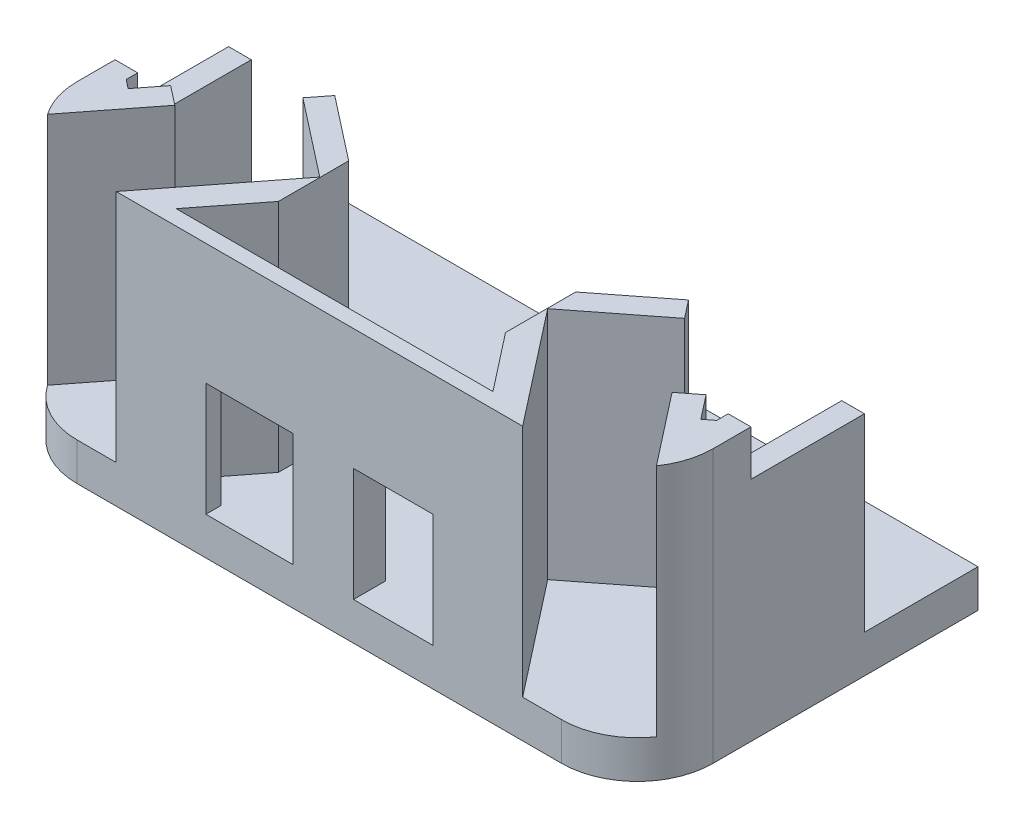
SolidWorks part; units mm, degrees
ref_plane "前视基准面" through (0, 0, 0) normal (0, 0, 1) x (1, 0, 0)
ref_plane "上视基准面" through (0, 0, 0) normal (0, 1, 0) x (1, 0, 0)
ref_plane "右视基准面" through (0, 0, 0) normal (1, 0, 0) x (0, 0, -1)
sketch "草图1" plane through (0, 0, 0) normal (0, 1, 0) x (1, 0, 0)
  line L1 (-42, 15) -> (42, 15)
  line L2 (-42, 15) -> (-42, -15)
  line L3 (-42, -15) -> (42, -15)
  line L4 (42, 15) -> (42, -15)
  line L5 (-42, 15) -> (42, -15) construction
  line L6 (-42, -15) -> (42, 15) construction
  point P0 (0, 0)
  dimension "D1" = 84
  dimension "D2" = 30
extrude "凸台-拉伸1" add sketch "草图1" along normal blind 34
sketch "草图2" plane through (0, 34, 0) normal (0, 1, 0) x (1, 0, 0)
  line L0 (-39, 15) -> (-3.1616, -13)
  line L1 (42, 15) -> (-42, 15) construction
  line L2 (-3.1616, -13) -> (3.1616, -13)
  line L3 (3.1616, -13) -> (39, 15)
  line L4 (-39, 15) -> (39, 15)
  line L5 (-42, 15) -> (-42, -15) construction
  line L6 (-42, -15) -> (42, -15) construction
  dimension "D1" = 38
  dimension "D2" = 3
  dimension "D3" = 3
  dimension "D4" = 2
  dimension "D5" = 38
extrude "切除-拉伸1" cut sketch "草图2" against normal blind 30
sketch "草图3" plane through (0, 34, 0) normal (0, 1, 0) x (1, 0, 0)
  line L0 (-26.357, 5.1222) -> (-42, -14.9)
  line L1 (42, -14.9) -> (26.357, 5.1222)
  line L2 (-39, 15) -> (-3.1616, -13) construction
  line L3 (42, -15) -> (42, 15) construction
  line L4 (-42, 15) -> (-42, -15) construction
  line L5 (-42, -14.9) -> (-42, -15)
  line L6 (0, 15) -> (0, -15) construction
  line L7 (3.1616, -13) -> (39, 15) construction
  line L8 (-42, -15) -> (-26.8499, -15)
  line L9 (-42, -15) -> (42, -15) construction
  line L10 (-26.8499, -15) -> (-16.9008, -2.2658)
  line L11 (-16.9008, -2.2658) -> (-26.357, 5.1222)
  line L12 (26.357, 5.1222) -> (16.9008, -2.2658)
  line L13 (16.9008, -2.2658) -> (26.8499, -15)
  line L14 (26.8499, -15) -> (42, -15)
  line L15 (42, -15) -> (42, -14.9)
  dimension "D1" = 12
  dimension "D2" = 0.1
  dimension "D3" = 12
  dimension "D4" = 0.1
sketch "草图4" plane through (0, 0, 15) normal (0, 0, 1) x (1, 0, 0)
  line L0 (0, 34) -> (0, 0) construction
  line L1 (-42, 34) -> (42, 34) construction
  line L2 (-15, 34) -> (-15, 16)
  line L3 (-15, 34) -> (15, 34)
  line L4 (0, 34) -> (0, 16)
  line L5 (-15, 16) -> (15, 16)
  line L6 (15, 34) -> (15, 16)
  line M3 (42, 34) -> (-42, 34)
  dimension "D1" = 18
  dimension "D2" = 15
extrude "切除-拉伸4" cut sketch "草图4" against normal blind 30 contours L2 L5 L4 L3 | L6 L4 L5 M3 region at (-7.5, 25, 15) region at (7.5, 25, 15)
extrude "切除-拉伸6" cut sketch "草图3" against normal blind 30
sketch "草图6" plane through (0, 4, 0) normal (0, 1, 0) x (1, 0, 0)
  line L0 (-24.51, 7.4862) -> (-15.0538, 0.0983)
  line L1 (-26.357, 5.1222) -> (-42, -14.9) construction
  line L2 (-26.8499, -15) -> (-16.9008, -2.2658) construction
  line L3 (-15.0538, 0.0983) -> (-13.2069, 2.4623)
  line L4 (-13.2069, 2.4623) -> (-22.663, 9.8502)
  line L5 (-22.663, 9.8502) -> (-24.51, 7.4862)
  line L6 (13.2069, 2.4623) -> (22.663, 9.8502)
  line L7 (16.9008, -2.2658) -> (26.8499, -15) construction
  line L8 (42, -14.9) -> (26.357, 5.1222) construction
  line L9 (22.663, 9.8502) -> (24.51, 7.4862)
  line L10 (42, -14.9) -> (26.357, 5.1222) construction
  line L11 (24.51, 7.4862) -> (15.0538, 0.0983)
  line L12 (16.9008, -2.2658) -> (26.8499, -15) construction
  line L13 (15.0538, 0.0983) -> (13.2069, 2.4623)
  line L17 (-39, 15) -> (-26.357, 5.1222) construction
  line L18 (26.357, 5.1222) -> (39, 15) construction
  dimension "D1" = 3
  dimension "D2" = 3
  dimension "D3" = 3
  dimension "D4" = 3
sketch "草图8" plane through (0, 34, 0) normal (0, 1, 0) x (1, 0, 0)
  line L0 (42, -14.9) -> (42, 15) construction
  line L1 (-39, 15) -> (39, 15)
  line L2 (-39, 15) -> (-39, -13)
  line L3 (-39, -13) -> (39, -13)
  line L4 (39, 15) -> (39, -13)
  line L5 (26.8499, -15) -> (42, -15) construction
  dimension "D1" = 3
  dimension "D2" = 2
extrude "切除-拉伸7" cut sketch "草图8" against normal blind 30
extrude "凸台-拉伸4" add sketch "草图6" along normal blind 30
sketch "草图9" plane through (0, 4, 0) normal (0, 1, 0) x (1, 0, 0)
  line L0 (-25.2873, -13) -> (-13.2069, 2.4623)
  line L1 (-13.2069, 2.4623) -> (-13.2069, -13)
  line L2 (-25.2873, -13) -> (25.2873, -13) construction
  line L3 (-13.2069, -13) -> (-24.5296, -13)
  line L4 (0, -13) -> (0, 15) construction
  line L5 (-15, -13) -> (15, -13) construction
  line L6 (39, 15) -> (-39, 15) construction
  line L7 (13.2069, -13) -> (24.5296, -13)
  line L8 (13.2069, 2.4623) -> (13.2069, -13)
  line L9 (25.2873, -13) -> (13.2069, 2.4623)
  line M4 (-13.2069, 2.4623) -> (-15.0538, 0.0983)
  line M14 (-25.2873, -13) -> (25.2873, -13)
  line M17 (15.0538, 0.0983) -> (13.2069, 2.4623)
extrude "凸台-拉伸5" add sketch "草图9" along normal blind 30 contours L9 L8 M14 M17 | L1 L0 M4 M14 region at (17.2337, 4, 7.8459) region at (-17.2337, 4, 7.8459)
sketch "草图11" plane through (0, 0, 13) normal (0, 0, 1) x (1, 0, 0)
  line L1 (-15, 34) -> (15, 34)
  line L2 (-15, 34) -> (-15, 16)
  line L3 (-15, 16) -> (15, 16)
  line L4 (15, 34) -> (15, 16)
extrude "切除-拉伸9" cut sketch "草图11" against normal through all
sketch "草图14" plane through (0, 34, 0) normal (0, 1, 0) x (1, 0, 0)
  line L0 (-20.9247, -13) -> (-15, -5.4167)
  line L1 (-15, 3.8633) -> (-15, -15) construction
  line L2 (-15, -5.4167) -> (-15, -13)
  line L3 (-15, -13) -> (-20.9247, -13)
  line L4 (-26.8499, -15) -> (-15, -15) construction
  line L5 (-26.8499, -15) -> (-15.0538, 0.0983) construction
  line L6 (-15, -5.4167) -> (-15, -13)
  line L7 (0, 15) -> (0, -15) construction
  line L8 (39, 15) -> (-39, 15) construction
  line L9 (-15, -15) -> (15, -15) construction
  line L10 (15, -5.4167) -> (15, -13)
  line L11 (15, -13) -> (20.9247, -13)
  line L12 (15, -5.4167) -> (15, -13)
  line L13 (20.9247, -13) -> (15, -5.4167)
  line M1 (-15, -15) -> (-15, 3.8633)
  dimension "D1" = 2
  dimension "D2" = 0
extrude "切除-拉伸12" cut sketch "草图14" against normal blind 30 contours L3 L0 M1 | L11 L13 L10 region at (-16.9749, 34, 10.4722) region at (16.9749, 34, 10.4722)
sketch "草图17" plane through (0, 4, 0) normal (0, 1, 0) x (1, 0, 0)
  line L0 (-22.663, 9.8502) -> (-23.3928, 10.4204)
  line L1 (-23.3928, 10.4204) -> (-25.2397, 8.0564)
  line L2 (-25.2397, 8.0564) -> (-24.51, 7.4862)
  line L3 (-24.51, 7.4862) -> (-22.663, 9.8502)
  line L4 (22.663, 9.8502) -> (23.3597, 10.3946)
  line L5 (23.3597, 10.3946) -> (25.2067, 8.0305)
  line L6 (25.2067, 8.0305) -> (24.51, 7.4862)
  line L7 (24.51, 7.4862) -> (22.663, 9.8502)
extrude "凸台-拉伸6" add sketch "草图17" along normal blind 30
sketch "草图23" plane through (0, 4, 0) normal (0, 1, 0) x (1, 0, 0)
  line L0 (23.3597, 10.3946) -> (26.1177, 12.5494)
  line L1 (26.1177, 12.5494) -> (32.2744, 4.6693)
  line L2 (32.2744, 4.6693) -> (29.7527, 2.6992)
  line L3 (29.7527, 2.6992) -> (25.4431, 8.2152)
  line L4 (25.4431, 8.2152) -> (25.2067, 8.0305)
  line L5 (25.2067, 8.0305) -> (23.3597, 10.3946)
  line L6 (0, 15) -> (0, -15) construction
  line L7 (39, 15) -> (-39, 15) construction
  line L8 (-15, -15) -> (15, -15) construction
  line L9 (-25.2067, 8.0305) -> (-23.3597, 10.3946)
  line L10 (-25.4431, 8.2152) -> (-25.2067, 8.0305)
  line L11 (-29.7527, 2.6992) -> (-25.4431, 8.2152)
  line L12 (-32.2744, 4.6693) -> (-29.7527, 2.6992)
  line L13 (-26.1177, 12.5494) -> (-32.2744, 4.6693)
  line L14 (-23.3597, 10.3946) -> (-26.1177, 12.5494)
  dimension "D1" = 3.5
  dimension "D2" = 10
  dimension "D3" = 90
extrude "凸台-拉伸9" add sketch "草图23" along normal blind 8
sketch "草图25" plane through (0, 34, 0) normal (0, 1, 0) x (1, 0, 0)
  line L0 (-25.4431, 8.2152) -> (-42, -12.9766)
  line L1 (-42, 15) -> (-42, -14.9) construction
  line L2 (-42, -12.9766) -> (-42, -14.9)
  line L3 (-42, -14.9) -> (-39, -11.0602)
  line L4 (-39, -11.0602) -> (-39, -9.1368)
  line L5 (-39, 15) -> (-39, -11.0602) construction
  line L6 (0, 15) -> (0, -15) construction
  line L7 (39, 15) -> (-39, 15) construction
  line L8 (-15, -15) -> (15, -15) construction
  line L9 (39, -11.0602) -> (39, -9.1368)
  line L10 (42, -14.9) -> (39, -11.0602)
  line L11 (42, -12.9766) -> (42, -14.9)
  line L12 (42, -12.9766) -> (39, -9.1368)
  line M1 (-39, -11.0602) -> (-39, 15)
  line M3 (-42, 15) -> (-42, -14.9)
  line M4 (-42, -14.9) -> (-39, -11.0602)
extrude "切除-拉伸16" cut sketch "草图25" against normal blind 30 contours L0 M1 M3 M4 | L11 L12 L9 L10 region at (-40.5, 34, 12.0184) region at (40.5, 34, 12.0184)
sketch "草图26" plane through (0, 4, 0) normal (0, 1, 0) x (1, 0, 0)
  line L0 (-39, -9.1368) -> (-35.306, -4.4088)
  line L1 (-35.306, -4.4088) -> (-39, -1.5227)
  line L2 (-39, 15) -> (-39, -9.1368) construction
  line L3 (-39, -1.5227) -> (-39, -9.1368)
  line L4 (0, 0) -> (0, -15) construction
  line L5 (-15, -15) -> (15, -15) construction
  line L6 (39, -1.5227) -> (39, -9.1368)
  line L7 (35.306, -4.4088) -> (39, -1.5227)
  line L8 (39, -9.1368) -> (35.306, -4.4088)
  line L9 (25.4431, 8.2152) -> (29.7527, 2.6992) construction
  dimension "D1" = 6
  dimension "D2" = 180
extrude "凸台-拉伸10" add sketch "草图26" along normal blind 30
sketch "草图27" plane through (0, 0, -15) normal (0, 0, -1) x (-1, 0, 0)
  line L0 (42, 34) -> (42, 0) construction
  line L1 (-42, 0) -> (42, 0)
  line L2 (-42, 0) -> (-42, 1)
  line L3 (-42, 1) -> (42, 1)
  line L4 (42, 0) -> (42, 1)
  dimension "D1" = 1
extrude "切除-拉伸17" cut sketch "草图27" against normal through all
sketch "草图28" plane through (0, 16, 0) normal (0, 1, 0) x (1, 0, 0)
  line L0 (-15, -15) -> (15, -15) construction
  line L1 (-13.2069, -13) -> (13.2069, -13)
  line L2 (-13.2069, -13) -> (-13.2069, -15)
  line L3 (-13.2069, -15) -> (13.2069, -15)
  line L4 (13.2069, -13) -> (13.2069, -15)
extrude "切除-拉伸18" cut sketch "草图28" against normal blind 12
sketch "草图29" plane through (-15, 0, 0) normal (1, 0, 0) x (0, 0, -1)
  line L1 (-13, 34) -> (-15, 34)
  line L2 (-13, 34) -> (-13, 16)
  line L3 (-13, 16) -> (-15, 16)
  line L4 (-15, 34) -> (-15, 16)
extrude "凸台-拉伸11" add sketch "草图29" along normal blind 30
sketch "草图30" plane through (0, 16, 0) normal (0, 1, 0) x (1, 0, 0)
  line L0 (-26.8499, -15) -> (26.8499, -15) construction
  line L1 (-15, 3.8633) -> (15, 3.8633)
  line L2 (-15, 3.8633) -> (-15, -15)
  line L3 (-15, -15) -> (15, -15)
  line L4 (15, 3.8633) -> (15, -15)
extrude "切除-拉伸19" cut sketch "草图30" against normal blind 12
sketch "草图31" plane through (0, 0, 15) normal (0, 0, 1) x (1, 0, 0)
  line L1 (-15, 16) -> (15, 16)
  line L2 (-15, 16) -> (-15, 19)
  line L3 (-15, 19) -> (15, 19)
  line L4 (15, 16) -> (15, 19)
extrude "切除-拉伸20" cut sketch "草图31" against normal blind 12
sketch "草图32" plane through (-42, 0, 0) normal (-1, 0, 0) x (0, 0, 1)
  line L1 (-15, 34) -> (0, 34)
  line L2 (-15, 34) -> (-15, 29)
  line L3 (-15, 29) -> (0, 29)
  line L4 (0, 34) -> (0, 29)
  dimension "D1" = 15
extrude "切除-拉伸21" cut sketch "草图32" against normal blind 10
sketch "草图33" plane through (42, 0, 0) normal (1, 0, 0) x (0, 0, -1)
  line L0 (-12.9766, 34) -> (15, 34) construction
  line L1 (15, 34) -> (0, 34)
  line L2 (15, 34) -> (15, 29)
  line L3 (15, 29) -> (0, 29)
  line L4 (0, 34) -> (0, 29)
  line L5 (15, 34) -> (15, 1) construction
  dimension "D1" = 15
extrude "切除-拉伸22" cut sketch "草图33" against normal blind 10
sketch "草图39" plane through (0, 0, -15) normal (0, 0, -1) x (-1, 0, 0)
  line L0 (0, 4) -> (0, 1) construction
  line L1 (-39, 4) -> (39, 4) construction
  line L2 (42, 1) -> (-42, 1) construction
  line L4 (-15, 4) -> (15, 4)
  line L5 (-15, 4) -> (-15, 1)
  line L6 (-15, 1) -> (15, 1)
  line L7 (15, 4) -> (15, 1)
  line L8 (-15, 4) -> (15, 1) construction
  line L9 (-15, 1) -> (15, 4) construction
  point P6 (0, 2.5)
extrude "凸台-拉伸12" add sketch "草图39" along normal blind 1
chamfer "倒角1" distance 10 angle 30 2 edges at (-15, 2.5, -15) (15, 2.5, -15) first distance on face at (-32, 11.3333, -15) first distance on face at (32, 11.3333, -15)
sketch "草图41" plane through (0, 4, 0) normal (0, 1, 0) x (1, 0, 0)
  line L0 (-32.2744, 4.6693) -> (-37.8277, -2.4386)
  line L1 (-35.306, -4.4088) -> (-39, -1.5227) construction
  line L2 (-37.8277, -2.4386) -> (-35.306, -4.4088)
  line L3 (-35.306, -4.4088) -> (-29.7527, 2.6992)
  line L4 (-29.7527, 2.6992) -> (-32.2744, 4.6693)
  line L5 (29.7527, 2.6992) -> (35.306, -4.4088)
  line L6 (32.2744, 4.6693) -> (37.8277, -2.4386)
  line L7 (39, -1.5227) -> (35.306, -4.4088) construction
  line L8 (37.8277, -2.4386) -> (35.306, -4.4088)
  line L9 (29.7527, 2.6992) -> (32.2744, 4.6693)
extrude "凸台-拉伸13" add sketch "草图41" along normal blind 8
sketch "草图42" plane through (0, 12, 0) normal (0, 1, 0) x (1, 0, 0)
  line L0 (35.306, -4.4088) -> (32.8434, -1.2567)
  line L1 (25.4431, 8.2152) -> (35.306, -4.4088) construction
  line L2 (32.8434, -1.2567) -> (35.365, 0.7134)
  line L3 (37.8277, -2.4386) -> (26.1177, 12.5494) construction
  line L4 (35.365, 0.7134) -> (37.8277, -2.4386)
  line L5 (39, -1.5227) -> (35.306, -4.4088) construction
  line L6 (35.306, -4.4088) -> (37.8277, -2.4386) construction
  line L7 (37.8277, -2.4386) -> (35.306, -4.4088)
  line L8 (0, 16) -> (0, 0) construction
  line L9 (-23.2679, 16) -> (23.2679, 16) construction
  line L10 (-37.8277, -2.4386) -> (-35.306, -4.4088)
  line L11 (-35.365, 0.7134) -> (-37.8277, -2.4386)
  line L12 (-32.8434, -1.2567) -> (-35.365, 0.7134)
  line L13 (-35.306, -4.4088) -> (-32.8434, -1.2567)
  dimension "D1" = 4
extrude "凸台-拉伸14" add sketch "草图42" along normal blind 22
fillet "圆角1" radius 10 2 edges at (42, 2.5, 15) (-42, 2.5, 15)
sketch "草图44" plane through (0, 4, 0) normal (0, 1, 0) x (1, 0, 0)
  line L0 (0, -15) -> (0, 16) construction
  line L1 (-15, -15) -> (15, -15) construction
  line L2 (-23.2679, 16) -> (23.2679, 16) construction
  line L4 (0, -15) -> (-3.5, -15)
  line L5 (0, -15) -> (0, -10.8)
  line L6 (0, -10.8) -> (-3.5, -10.8)
  line L7 (-3.5, -15) -> (-3.5, -10.8)
  line L8 (0, -15) -> (4.5, -15)
  line L9 (0, -15) -> (0, -10.8)
  line L10 (0, -10.8) -> (4.5, -10.8)
  line L11 (4.5, -15) -> (4.5, -10.8)
  line M24 (-15, -15) -> (15, -15)
  dimension "D1" = 4.2
  dimension "D2" = 4.5
  dimension "D3" = 3.5
extrude "凸台-拉伸16" add sketch "草图44" along normal blind 15 contours L7 L5 L6 M24 | L11 L10 L5 M24 region at (-1.75, 4, 12.9) region at (2.25, 4, 12.9)
sketch "草图46" plane through (0, 29, 0) normal (0, 1, 0) x (1, 0, 0)
  line L0 (32.8434, -1.2567) -> (40.2187, -10.6967) construction
  line L1 (42, -5) -> (42, 0) construction
  line L2 (42, 0) -> (39, 0) construction
  line L3 (39, 0) -> (39, -1.5227) construction
  line L4 (39, -1.5227) -> (37.8277, -2.4386) construction
  line L5 (37.8277, -2.4386) -> (35.365, 0.7134) construction
  line L6 (35.365, 0.7134) -> (32.8434, -1.2567) construction
  line L7 (15, -5.4167) -> (20.9247, -13) construction
  line L8 (20.9247, -13) -> (-20.9247, -13) construction
  line L9 (-20.9247, -13) -> (-15, -5.4167) construction
  line L10 (-15, -5.4167) -> (-15, 3.8633) construction
  line L11 (-15, 3.8633) -> (-23.3928, 10.4204) construction
  line L12 (-23.3928, 10.4204) -> (-25.2397, 8.0564) construction
  line L13 (-25.2397, 8.0564) -> (-15.0538, 0.0983) construction
  line L14 (-15.0538, 0.0983) -> (-26.8499, -15) construction
  line L15 (-26.8499, -15) -> (26.8499, -15) construction
  line L16 (26.8499, -15) -> (15.0538, 0.0983) construction
  line L17 (15.0538, 0.0983) -> (25.2067, 8.0305) construction
  line L18 (25.2067, 8.0305) -> (23.3597, 10.3946) construction
  line L19 (23.3597, 10.3946) -> (15, 3.8633) construction
  line L20 (15, 3.8633) -> (15, -5.4167) construction
  line L21 (-42, 0) -> (-42, -5) construction
  line L22 (-40.2187, -10.6967) -> (-32.8434, -1.2567) construction
  line L23 (-32.8434, -1.2567) -> (-35.365, 0.7134) construction
  line L24 (-35.365, 0.7134) -> (-37.8277, -2.4386) construction
  line L25 (-37.8277, -2.4386) -> (-39, -1.5227) construction
  line L26 (-39, -1.5227) -> (-39, 0) construction
  line L27 (-39, 0) -> (-42, 0) construction
  line L28 (32.8434, -1.2567) -> (40.2187, -10.6967)
  line L29 (42, -5) -> (42, 0)
  line L30 (42, 0) -> (39, 0)
  line L31 (39, 0) -> (39, -1.5227)
  line L32 (39, -1.5227) -> (37.8277, -2.4386)
  line L33 (37.8277, -2.4386) -> (35.365, 0.7134)
  line L34 (35.365, 0.7134) -> (32.8434, -1.2567)
  line L35 (15, -5.4167) -> (20.9247, -13)
  line L36 (20.9247, -13) -> (-20.9247, -13)
  line L37 (-20.9247, -13) -> (-15, -5.4167)
  line L38 (-15, -5.4167) -> (-15, 3.8633)
  line L39 (-15, 3.8633) -> (-23.3928, 10.4204)
  line L40 (-23.3928, 10.4204) -> (-25.2397, 8.0564)
  line L41 (-25.2397, 8.0564) -> (-15.0538, 0.0983)
  line L42 (-15.0538, 0.0983) -> (-26.8499, -15)
  line L43 (-26.8499, -15) -> (26.8499, -15)
  line L44 (26.8499, -15) -> (15.0538, 0.0983)
  line L45 (15.0538, 0.0983) -> (25.2067, 8.0305)
  line L46 (25.2067, 8.0305) -> (23.3597, 10.3946)
  line L47 (23.3597, 10.3946) -> (15, 3.8633)
  line L48 (15, 3.8633) -> (15, -5.4167)
  line L49 (-42, 0) -> (-42, -5)
  line L50 (-40.2187, -10.6967) -> (-32.8434, -1.2567)
  line L51 (-32.8434, -1.2567) -> (-35.365, 0.7134)
  line L52 (-35.365, 0.7134) -> (-37.8277, -2.4386)
  line L53 (-37.8277, -2.4386) -> (-39, -1.5227)
  line L54 (-39, -1.5227) -> (-39, 0)
  line L55 (-39, 0) -> (-42, 0)
  arc A0 (40.2187, -10.6967) -> (42, -5) centre (32, -5) ccw construction
  arc A1 (-42, -5) -> (-40.2187, -10.6967) centre (-32, -5) ccw construction
  arc A2 (40.2187, -10.6967) -> (42, -5) centre (32, -5) ccw
  arc A3 (-42, -5) -> (-40.2187, -10.6967) centre (-32, -5) ccw
sketch "草图47" plane through (0, 34, 0) normal (0, 1, 0) x (1, 0, 0)
  line L0 (32.8434, -1.2567) -> (40.2187, -10.6967) construction
  line L1 (42, -5) -> (42, 0) construction
  line L2 (42, 0) -> (39, 0) construction
  line L3 (39, 0) -> (39, -1.5227) construction
  line L4 (39, -1.5227) -> (37.8277, -2.4386) construction
  line L5 (37.8277, -2.4386) -> (35.365, 0.7134) construction
  line L6 (35.365, 0.7134) -> (32.8434, -1.2567) construction
  line L7 (-42, 0) -> (-42, -5) construction
  line L8 (-40.2187, -10.6967) -> (-32.8434, -1.2567) construction
  line L9 (-32.8434, -1.2567) -> (-35.365, 0.7134) construction
  line L10 (-35.365, 0.7134) -> (-37.8277, -2.4386) construction
  line L11 (-37.8277, -2.4386) -> (-39, -1.5227) construction
  line L12 (-39, -1.5227) -> (-39, 0) construction
  line L13 (-39, 0) -> (-42, 0) construction
  line L14 (15, -5.4167) -> (20.9247, -13) construction
  line L15 (20.9247, -13) -> (-20.9247, -13) construction
  line L16 (-20.9247, -13) -> (-15, -5.4167) construction
  line L17 (-15, -5.4167) -> (-15, 3.8633) construction
  line L18 (-15, 3.8633) -> (-23.3928, 10.4204) construction
  line L19 (-23.3928, 10.4204) -> (-25.2397, 8.0564) construction
  line L20 (-25.2397, 8.0564) -> (-15.0538, 0.0983) construction
  line L21 (-15.0538, 0.0983) -> (-26.8499, -15) construction
  line L22 (-26.8499, -15) -> (26.8499, -15) construction
  line L23 (26.8499, -15) -> (15.0538, 0.0983) construction
  line L24 (15.0538, 0.0983) -> (25.2067, 8.0305) construction
  line L25 (25.2067, 8.0305) -> (23.3597, 10.3946) construction
  line L26 (23.3597, 10.3946) -> (15, 3.8633) construction
  line L27 (15, 3.8633) -> (15, -5.4167) construction
  line L28 (32.8434, -1.2567) -> (40.2187, -10.6967)
  line L29 (42, -5) -> (42, 0)
  line L30 (42, 0) -> (39, 0)
  line L31 (39, 0) -> (39, -1.5227)
  line L32 (39, -1.5227) -> (37.8277, -2.4386)
  line L33 (37.8277, -2.4386) -> (35.365, 0.7134)
  line L34 (35.365, 0.7134) -> (32.8434, -1.2567)
  line L35 (-42, 0) -> (-42, -5)
  line L36 (-40.2187, -10.6967) -> (-32.8434, -1.2567)
  line L37 (-32.8434, -1.2567) -> (-35.365, 0.7134)
  line L38 (-35.365, 0.7134) -> (-37.8277, -2.4386)
  line L39 (-37.8277, -2.4386) -> (-39, -1.5227)
  line L40 (-39, -1.5227) -> (-39, 0)
  line L41 (-39, 0) -> (-42, 0)
  line L42 (15, -5.4167) -> (20.9247, -13)
  line L43 (20.9247, -13) -> (-20.9247, -13)
  line L44 (-20.9247, -13) -> (-15, -5.4167)
  line L45 (-15, -5.4167) -> (-15, 3.8633)
  line L46 (-15, 3.8633) -> (-23.3928, 10.4204)
  line L47 (-23.3928, 10.4204) -> (-25.2397, 8.0564)
  line L48 (-25.2397, 8.0564) -> (-15.0538, 0.0983)
  line L49 (-15.0538, 0.0983) -> (-26.8499, -15)
  line L50 (-26.8499, -15) -> (26.8499, -15)
  line L51 (26.8499, -15) -> (15.0538, 0.0983)
  line L52 (15.0538, 0.0983) -> (25.2067, 8.0305)
  line L53 (25.2067, 8.0305) -> (23.3597, 10.3946)
  line L54 (23.3597, 10.3946) -> (15, 3.8633)
  line L55 (15, 3.8633) -> (15, -5.4167)
  arc A0 (40.2187, -10.6967) -> (42, -5) centre (32, -5) ccw construction
  arc A1 (-42, -5) -> (-40.2187, -10.6967) centre (-32, -5) ccw construction
  arc A2 (40.2187, -10.6967) -> (42, -5) centre (32, -5) ccw
  arc A3 (-42, -5) -> (-40.2187, -10.6967) centre (-32, -5) ccw
extrude "凸台-拉伸17" add sketch "草图47" along normal blind 1
sketch "草图50" plane through (0, 1, 0) normal (0, -1, 0) x (1, 0, 0)
  line L8 (42, -15) -> (42, 5)
  line L9 (32, 15) -> (-32, 15)
  line L10 (-42, 5) -> (-42, -15)
  line L11 (-42, -15) -> (-25, -15)
  line L12 (-42, -15) -> (-25, -15)
  line L13 (-25, -15) -> (-23.2679, -16)
  line L14 (-25, -15) -> (-23.2679, -16)
  line L15 (-23.2679, -16) -> (23.2679, -16)
  line L16 (42, -15) -> (42, 5)
  line L17 (32, 15) -> (-32, 15)
  line L18 (-42, 5) -> (-42, -15)
  line L24 (-23.2679, -16) -> (23.2679, -16)
  line L25 (23.2679, -16) -> (25, -15)
  line L26 (23.2679, -16) -> (25, -15)
  line L27 (25, -15) -> (42, -15)
  line L28 (25, -15) -> (42, -15)
  arc A2 (42, 5) -> (32, 15) centre (32, 5) ccw
  arc A3 (-32, 15) -> (-42, 5) centre (-32, 5) ccw
  arc A4 (42, 5) -> (32, 15) centre (32, 5) ccw
  arc A5 (-32, 15) -> (-42, 5) centre (-32, 5) ccw
  dimension "D1" = 0
extrude "凸台-拉伸20" add sketch "草图50" along normal blind 2
sketch "草图51" plane through (0, 4, 0) normal (0, 1, 0) x (1, 0, 0)
  line L0 (-42, 15) -> (-25, 15)
  line L1 (-25, 15) -> (-23.2679, 16)
  line L2 (-23.2679, 16) -> (23.2679, 16)
  line L3 (23.2679, 16) -> (25, 15)
  line L4 (25, 15) -> (42, 15)
  line L5 (42, 15) -> (42, 30)
  line L6 (42, 30) -> (-42, 30)
  line L7 (-42, 30) -> (-42, 15)
  dimension "D1" = 15
extrude "凸台-拉伸21" add sketch "草图51" against normal blind 5
sketch "草图52" plane through (0, -1, 0) normal (0, -1, 0) x (1, 0, 0)
  circle A0 centre (35, -17) radius 1.75
  circle A1 centre (9, -23) radius 1.75
  circle A2 centre (-9, -23) radius 1.75
  circle A3 centre (-35, -17) radius 1.75
extrude "切除-拉伸23" cut sketch "草图52" against normal blind 10
